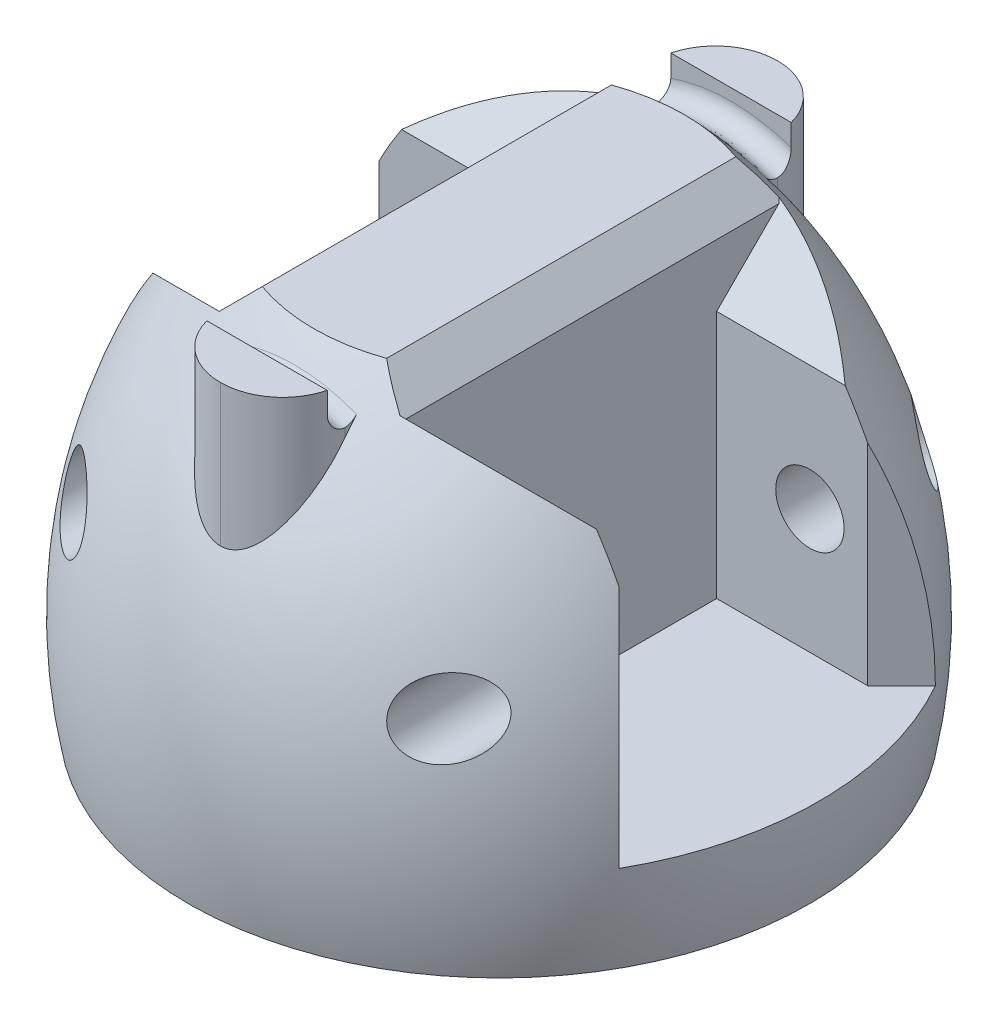
SolidWorks part; units mm, degrees
ref_plane "前基準面" through (0, 0, 0) normal (0, 0, 1) x (1, 0, 0)
ref_plane "上基準面" through (0, 0, 0) normal (0, 1, 0) x (1, 0, 0)
ref_plane "右基準面" through (0, 0, 0) normal (1, 0, 0) x (0, 0, -1)
sketch "草圖2" plane through (0, 0, 0) normal (0, 0, 1) x (1, 0, 0)
  line L0 (0, 0) -> (0, 18)
  line L1 (0, 0) -> (10, 0)
  arc A0 (0, 18) -> (10, 0) centre (-5.7062, 3.0521) cw
  point P4 (-3.8242, 3.7129)
  point P6 (0, 0)
  point P7 (-0.6437, 5.3032)
  point P8 (-9.3939, 0.9281)
  dimension "D3" = 16
  dimension "D1" = 10
  dimension "D2" = 18
revolve "旋轉1" add sketch "草圖2" angle 360 about L0
sketch "草圖3" plane through (0, 0, 0) normal (0, -1, 0) x (1, 0, 0)
  line L0 (0, 0) -> (0, -10) construction
  line L1 (0, 0) -> (-3.8268, -9.2388) construction
  line L2 (-0.5, -2.1) -> (-0.5, -1.5706)
  line L3 (0, 0) -> (-7.0711, -7.0711) construction
  line L4 (-1.1314, -1.8385) -> (-0.757, -1.4641)
  line L5 (-1.8385, -1.1314) -> (-1.4641, -0.757)
  line L6 (-2.1, -0.5) -> (-1.5706, -0.5)
  line L7 (-2.1, 0.5) -> (-1.5706, 0.5)
  line L8 (-1.8385, 1.1314) -> (-1.4641, 0.757)
  line L9 (-1.1314, 1.8385) -> (-0.757, 1.4641)
  line L10 (-0.5, 2.1) -> (-0.5, 1.5706)
  line L11 (0.5, 2.1) -> (0.5, 1.5706)
  line L12 (1.1314, 1.8385) -> (0.757, 1.4641)
  line L13 (1.8385, 1.1314) -> (1.4641, 0.757)
  line L14 (2.1, 0.5) -> (1.5706, 0.5)
  line L15 (2.1, -0.5) -> (1.5706, -0.5)
  line L16 (1.8385, -1.1314) -> (1.4641, -0.757)
  line L17 (1.1314, -1.8385) -> (0.757, -1.4641)
  line L18 (0.5, -2.1) -> (0.5, -1.5706)
  circle A0 centre (0, 0) radius 10 construction
  arc A1 (-0.5, -1.5706) -> (-0.757, -1.4641) centre (-0.6506, -1.5706) ccw
  arc A2 (0, -2.6) -> (-0.5, -2.1) centre (0, -2.1) cw
  arc A3 (-1.8385, -1.8385) -> (-1.1314, -1.8385) centre (-1.4849, -1.4849) ccw
  arc A4 (-1.8385, -1.8385) -> (-1.8385, -1.1314) centre (-1.4849, -1.4849) cw
  arc A5 (-1.4641, -0.757) -> (-1.5706, -0.5) centre (-1.5706, -0.6506) ccw
  arc A6 (-2.6, 0) -> (-2.1, -0.5) centre (-2.1, 0) ccw
  arc A7 (-2.6, 0) -> (-2.1, 0.5) centre (-2.1, 0) cw
  arc A8 (-1.5706, 0.5) -> (-1.4641, 0.757) centre (-1.5706, 0.6506) ccw
  arc A9 (-1.8385, 1.8385) -> (-1.8385, 1.1314) centre (-1.4849, 1.4849) ccw
  arc A10 (-1.8385, 1.8385) -> (-1.1314, 1.8385) centre (-1.4849, 1.4849) cw
  arc A11 (-0.757, 1.4641) -> (-0.5, 1.5706) centre (-0.6506, 1.5706) ccw
  arc A12 (0, 2.6) -> (-0.5, 2.1) centre (0, 2.1) ccw
  arc A13 (0, 2.6) -> (0.5, 2.1) centre (0, 2.1) cw
  arc A14 (0.5, 1.5706) -> (0.757, 1.4641) centre (0.6506, 1.5706) ccw
  arc A15 (1.8385, 1.8385) -> (1.1314, 1.8385) centre (1.4849, 1.4849) ccw
  arc A16 (1.8385, 1.8385) -> (1.8385, 1.1314) centre (1.4849, 1.4849) cw
  arc A17 (1.4641, 0.757) -> (1.5706, 0.5) centre (1.5706, 0.6506) ccw
  arc A18 (2.6, 0) -> (2.1, 0.5) centre (2.1, 0) ccw
  arc A19 (2.6, 0) -> (2.1, -0.5) centre (2.1, 0) cw
  arc A20 (1.5706, -0.5) -> (1.4641, -0.757) centre (1.5706, -0.6506) ccw
  arc A21 (1.8385, -1.8385) -> (1.8385, -1.1314) centre (1.4849, -1.4849) ccw
  arc A22 (1.8385, -1.8385) -> (1.1314, -1.8385) centre (1.4849, -1.4849) cw
  arc A23 (0.757, -1.4641) -> (0.5, -1.5706) centre (0.6506, -1.5706) ccw
  arc A24 (0, -2.6) -> (0.5, -2.1) centre (0, -2.1) ccw
  point P14 (-0.5929, -1.4315)
  point P83 (0, 0)
  dimension "D2" = 1.7
  dimension "D3" = 22.5
  dimension "D4" = 2.1
  dimension "D1" = 0.5
extrude "除料-伸長1" cut sketch "草圖3" against normal blind 7
sketch "草圖4" plane through (0, 0, 0) normal (0, -1, 0) x (1, 0, 0)
  circle A1 centre (0, 0) radius 3.5
  dimension "D1" = 7
extrude "除料-伸長2" [suppressed] cut sketch "草圖4" against normal blind 1
sketch "草圖5" plane through (0, 0, 0) normal (0, -1, 0) x (1, 0, 0)
  circle A0 centre (0, 0) radius 1
  dimension "D1" = 2
extrude "除料-伸長3" cut sketch "草圖5" against normal blind 9
ref_plane "平面1" through (0, 3, 0) normal (0, -1, 0) x (-1, 0, 0)
sketch "草圖6" plane through (0, 3, 0) normal (0, -1, 0) x (-1, 0, 0)
  line L0 (-3, 0) -> (3, 0) construction
  line L5 (3, 4) -> (7.86, 4)
  line L6 (3, 4) -> (3, -4)
  line L7 (3, -4) -> (7.86, -4)
  line L8 (10.6878, 3.9569) -> (10.6878, -5.6556)
  line L9 (10.6878, -5.6556) -> (10.6878, -6.8278)
  line L10 (10.6878, -6.8278) -> (7.86, -4)
  line L11 (10.6878, 3.9569) -> (10.6878, 6.8278)
  line L12 (10.6878, 6.8278) -> (7.86, 4)
  line L13 (7.86, 4) -> (7.86, -4) construction
  line L14 (0, 55) -> (0, -55) construction
  line L15 (-3, 4) -> (-3, -4)
  line L16 (-3, 4) -> (-7.86, 4)
  line L17 (-10.6878, 6.8278) -> (-7.86, 4)
  line L18 (-10.6878, 3.9569) -> (-10.6878, 6.8278)
  line L19 (-10.6878, 3.9569) -> (-10.6878, -5.6556)
  line L20 (-10.6878, -5.6556) -> (-10.6878, -6.8278)
  line L21 (-3, -4) -> (-7.86, -4)
  line L22 (-10.6878, -6.8278) -> (-7.86, -4)
  point P10 (0, 0)
  point P15 (10.644, -5.6125)
  point P17 (0, 0)
  point P24 (0, 0)
  dimension "D1" = 8
  dimension "D2" = 3
  dimension "D3" = 4.86
  dimension "D4" = 45
  dimension "D5" = 45
extrude "除料-伸長4" cut sketch "草圖6" against normal blind 15
sketch "草圖7" plane through (0, 0, 4) normal (0, 0, -1) x (-1, 0, 0)
  line L0 (6, 7) -> (-6, 7) construction
  line L1 (6, 7) -> (-6, 7) construction
  line L2 (3, 3) -> (7.86, 3) construction
  line L5 (0, 0) -> (0, 7) construction
  line L6 (-10, 0) -> (10, 0) construction
  circle A0 centre (6, 7) radius 1.1
  circle A1 centre (-6, 7) radius 1.1
  point P4 (0, 0)
  point P5 (-6.1397, 7)
  point P11 (0, 7)
  dimension "D1" = 2.2
  dimension "D2" = 12
  dimension "D3" = 4
extrude "除料-伸長5" cut sketch "草圖7" against normal through all both and the other way through all
sketch "草圖8" plane through (3, 0, 0) normal (1, 0, 0) x (0, 0, -1)
  line L0 (-4, 11) -> (-11.6285, 18.6285)
  line L1 (-4, 9.7611) -> (-4, 14.9423) construction
  line L2 (-11.6285, 18.6285) -> (11.6285, 18.6285)
  line L3 (11.6285, 18.6285) -> (4, 11)
  line L4 (4, 14.9423) -> (4, 9.7611) construction
  line L5 (4, 11) -> (-4, 11)
  line L6 (-8.25, 3) -> (8.25, 3) construction
  line L7 (-4, 14.9423) -> (-4, 3) construction
  line L8 (4, 14.9423) -> (4, 3) construction
  dimension "D1" = 8
  dimension "D2" = 45
  dimension "D3" = 45
extrude "除料-伸長6" cut sketch "草圖8" along normal blind 10
mirror "鏡射1" about plane through (0, 0, 0) normal (1, 0, 0) of "除料-伸長6"
sketch "草圖9" plane through (3, 0, 0) normal (1, 0, 0) x (0, 0, -1)
  line L0 (-4, 3) -> (4, 3) construction
  line L1 (-8.7625, 14) -> (7.9165, 14)
  line L2 (-8.7625, 14) -> (-8.7625, 20.8659)
  line L3 (-8.7625, 20.8659) -> (7.9165, 20.8659)
  line L4 (7.9165, 14) -> (7.9165, 20.8659)
  dimension "D1" = 11
extrude "除料-伸長7" cut sketch "草圖9" against normal through all both and the other way through all
chamfer "導角1" distance 1 angle 45 2 edges at (-3, 14, 0) (3, 14, 0)
sketch "草圖10" plane through (0, 0, 0) normal (1, 0, 0) x (0, 0, -1)
  line L0 (5.6164, 14) -> (-5.6164, 14) construction
  line L1 (8.9619, 14) -> (7.4619, 14)
  line L2 (8.9619, 14) -> (8.9619, 8)
  line L3 (8.9619, 8) -> (7.4619, 8)
  line L4 (7.4619, 14) -> (7.4619, 8)
  line L5 (-7.4619, 8) -> (-8.9619, 8)
  line L6 (-7.4619, 8) -> (-7.4619, 14)
  line L7 (-7.4619, 14) -> (-8.9619, 14)
  line L8 (-8.9619, 8) -> (-8.9619, 14)
  point P12 (0, 0)
  dimension "D1" = 1.5
  dimension "D2" = 1.5
  dimension "D3" = 1.5
  dimension "D4" = 6
extrude "填料-伸長1" add sketch "草圖10" along normal mid plane 4
fillet "圓角1" radius 0.5 2 edges at (0.5542, 12.1108, -7.4619) (-0.5542, 12.1108, 7.4619)
fillet "圓角2" radius 2 4 edges at (-2, 11.4557, 8.9619) (2, 11.4557, 8.9619) (-2, 11.4557, -8.9619) (2, 11.4557, -8.9619)
